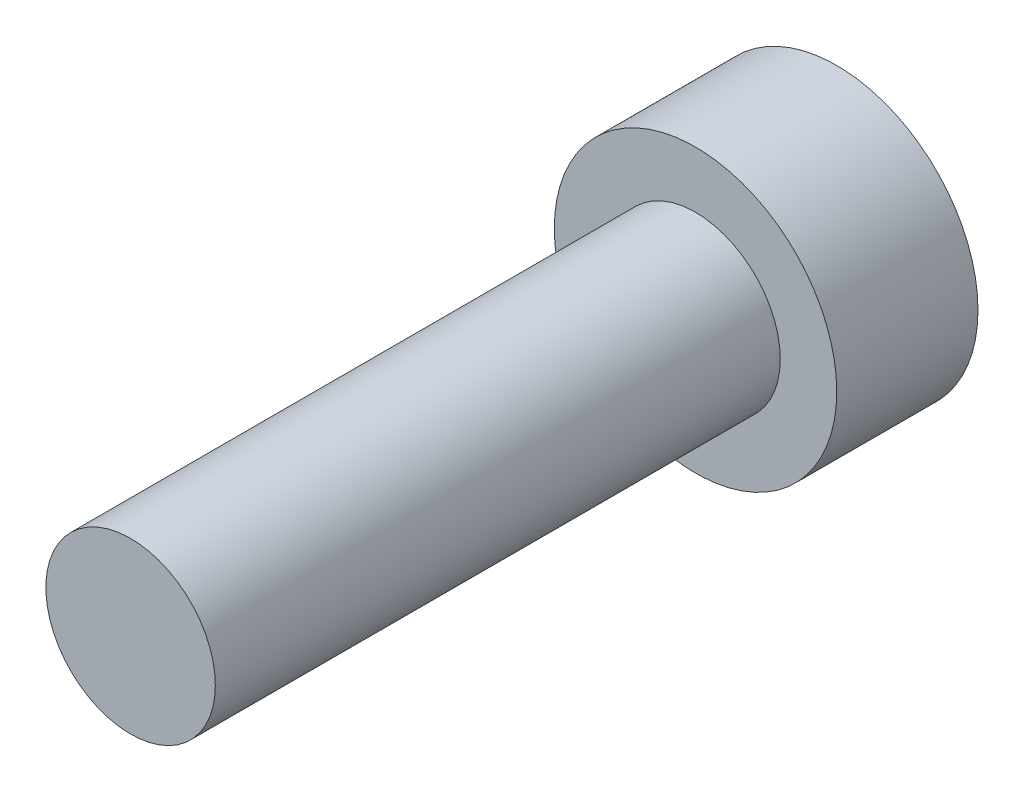
SolidWorks part; units mm, degrees
material "Chrome Stainless Steel"
ref_plane "Front Plane" through (0, 0, 0) normal (0, 0, 1) x (1, 0, 0)
ref_plane "Top Plane" through (0, 0, 0) normal (0, 1, 0) x (1, 0, 0)
ref_plane "Right Plane" through (0, 0, 0) normal (1, 0, 0) x (0, 0, -1)
sketch "Sketch1" plane through (0, 0, 0) normal (0, 0, 1) x (1, 0, 0)
  circle A0 centre (0, 0) radius 2.5
  circle A1 centre (0, 0) radius 1.5
  dimension "D1" = 5
  dimension "D2" = 3
extrude "Boss-Extrude3" add sketch "Sketch1" against normal blind 2.5 contours A0 A1 | A1 region at (-2.4293, 0, 0) region at (0, 0, 0)
extrude "Boss-Extrude4" add sketch "Sketch1<3>" along normal blind 10 contours A1 region at (0, 0, 0)
sketch "Sketch1<3>" plane through (0, 0, 0) normal (0, 0, 1) x (1, 0, 0) same geometry as "Sketch1"
